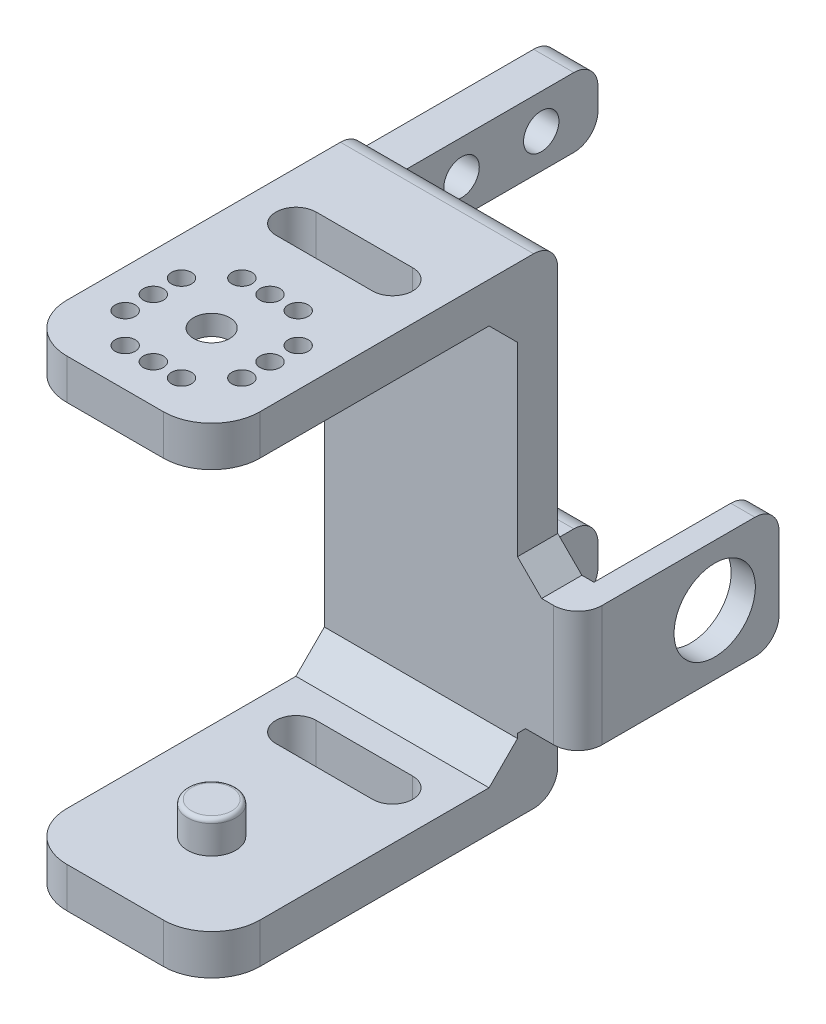
SolidWorks part; units mm, degrees
ref_plane "Front Plane" through (0, 0, 0) normal (0, 0, 1) x (1, 0, 0)
ref_plane "Top Plane" through (0, 0, 0) normal (0, 1, 0) x (1, 0, 0)
ref_plane "Right Plane" through (0, 0, 0) normal (1, 0, 0) x (0, 0, -1)
sketch "Sketch1" plane through (0, 0, 0) normal (1, 0, 0) x (0, 0, -1)
  line L0 (0, 59.7) -> (0, 0)
  line L1 (0, 0) -> (-43, 0)
  line L2 (-43, 0) -> (-43, 5)
  line L3 (-43, 5) -> (-8.5355, 5)
  line L4 (-5, 8.5355) -> (-5, 51.1645)
  line L5 (-8.5355, 54.7) -> (-43, 54.7)
  line L6 (-43, 54.7) -> (-43, 59.7)
  line L7 (-43, 59.7) -> (0, 59.7)
  line L8 (-8.5355, 54.7) -> (-5, 51.1645)
  line L9 (-5, 29.85) -> (0, 29.85) construction
  line L10 (-8.5355, 5) -> (-5, 8.5355)
  dimension "D1" = 49.7
  dimension "D2" = 5
  dimension "D3" = 5
  dimension "D4" = 5
  dimension "50" = 43
  dimension "D5" = 45
extrude "Boss-Extrude1" add sketch "Sketch1" along normal blind 24
sketch "Sketch2" plane through (0, 54.7, 0) normal (0, -1, 0) x (1, 0, 0)
  line L0 (24, 43) -> (0, 43) construction
  line L1 (12, 43) -> (12, 0) construction
  line L2 (24, 0) -> (0, 0) construction
  circle A0 centre (12, 31) radius 10.5
  dimension "D1" = 21
  dimension "D2" = 12
  dimension "D3" = 0
extrude "Cut-Extrude1" cut sketch "Sketch2" against normal blind 2.5
sketch "Sketch4" plane through (0, 57.2, 0) normal (0, -1, 0) x (1, 0, 0)
  circle A0 centre (12, 31) radius 2.25
  circle A1 centre (12, 31) radius 10.5 construction
  circle A2 centre (12, 38.25) radius 1.25
  circle A3 centre (8.5, 38.25) radius 1.25
  circle A4 centre (15.5, 38.25) radius 1.25
  circle A5 centre (19.25, 34.5) radius 1.25
  circle A6 centre (19.25, 31) radius 1.25
  circle A7 centre (19.25, 27.5) radius 1.25
  circle A8 centre (15.5, 23.75) radius 1.25
  circle A9 centre (12, 23.75) radius 1.25
  circle A10 centre (8.5, 23.75) radius 1.25
  circle A11 centre (4.75, 27.5) radius 1.25
  circle A12 centre (4.75, 31) radius 1.25
  circle A13 centre (4.75, 34.5) radius 1.25
  dimension "D1" = 4.5
  dimension "D2" = 0
  dimension "D3" = 2.5
  dimension "D4" = 7.25
  dimension "D5" = 3.5
  dimension "D6" = 3.5
  dimension "D7" = 4
extrude "Cut-Extrude2" cut sketch "Sketch4" against normal blind 10
sketch "Sketch11" plane through (0, 5, 0) normal (0, 1, 0) x (1, 0, 0)
  line L1 (24, -43) -> (0, -43) construction
  line L2 (12, -43) -> (12, -5) construction
  line L3 (24, -5) -> (0, -5) construction
  circle A0 centre (12, -31) radius 3
  dimension "D1" = 6
  dimension "D2" = 12
extrude "Boss-Extrude2" add sketch "Sketch11" along normal blind 4
sketch "Sketch12" plane through (0, 54.7, 0) normal (0, -1, 0) x (1, 0, 0)
  line L0 (12, 8.5355) -> (12, 20.5) construction
  line L2 (24, 8.5355) -> (0, 8.5355) construction
  line L3 (6, 12.0178) -> (18, 12.0178)
  line L10 (6, 17.0178) -> (18, 17.0178)
  line L11 (6, 12.0178) -> (18, 17.0178) construction
  line L12 (18, 12.0178) -> (6, 17.0178) construction
  line L17 (24, 43) -> (24, 0) construction
  circle A7 centre (12, 31) radius 10.5 construction
  arc A8 (18, 12.0178) -> (18, 17.0178) centre (18, 14.5178) ccw
  arc A9 (6, 12.0178) -> (6, 17.0178) centre (6, 14.5178) cw
  point P7 (12, 14.5178)
  point P18 (12, 14.5178)
  dimension "D1" = 5
  dimension "D2" = 6
extrude "Cut-Extrude5" cut sketch "Sketch12" against normal mid plane 130 contours A9 L10 A8 L3
sketch "Sketch13" plane through (0, 0, 0) normal (-1, 0, 0) x (0, 0, 1)
  line L0 (0, 8.6) -> (-24, 8.6)
  line L1 (0, 0) -> (0, 59.7) construction
  line L2 (-24, 8.6) -> (-24, 0)
  line L3 (-24, 0) -> (0, 0)
  line L4 (0, 0) -> (0, 8.6)
  line L5 (0, 28.85) -> (5, 28.85) construction
  line L11 (-12, 8.6) -> (-12, 0) construction
  line L12 (-24, 57.7) -> (0, 57.7)
  line L13 (-24, 49.1) -> (-24, 57.7)
  line L14 (0, 49.1) -> (-24, 49.1)
  line L15 (0, 57.7) -> (0, 49.1)
  line L16 (5, 51.1645) -> (5, 8.5355) construction
  circle A0 centre (-16.95, 4.3) radius 2.2
  circle A1 centre (-7.05, 4.3) radius 2.2
  circle A4 centre (-16.95, 53.4) radius 2.2
  circle A5 centre (-7.05, 53.4) radius 2.2
  dimension "D3" = 4.4
  dimension "D1" = 8.6
  dimension "D2" = 24
  dimension "D4" = 4.3
  dimension "D5" = 9.9
  dimension "D6" = 4.95
  dimension "D7" = 40.5
extrude "Boss-Extrude3" add sketch "Sketch13" against normal blind 5
sketch "Sketch14" plane through (24, 0, 0) normal (1, 0, 0) x (0, 0, -1)
  line L0 (-5, 10.1) -> (0, 10.1)
  line L1 (-5, 51.1645) -> (-5, 8.5355) construction
  line L2 (0, 0) -> (0, 59.7) construction
  line L3 (0, 10.1) -> (0, 25.1)
  line L4 (0, 25.1) -> (-5, 25.1)
  line L5 (-5, 25.1) -> (-5, 10.1)
  line L6 (-5, 17.6) -> (0, 17.6) construction
  line L7 (0, 8.6) -> (24, 8.6) construction
  dimension "D1" = 15
  dimension "D2" = 9
extrude "Boss-Extrude4" add sketch "Sketch14" along normal blind 7.5
sketch "Sketch15" plane through (0, 0, 0) normal (0, 0, -1) x (-1, 0, 0)
  line L0 (-31.5, 25.1) -> (-28.5, 25.1)
  line L1 (-31.5, 25.1) -> (-24, 25.1) construction
  line L2 (-28.5, 25.1) -> (-28.5, 10.1)
  line L3 (-31.5, 10.1) -> (-24, 10.1) construction
  line L4 (-28.5, 10.1) -> (-31.5, 10.1)
  line L5 (-31.5, 10.1) -> (-31.5, 25.1)
  dimension "D1" = 3
extrude "Boss-Extrude5" add sketch "Sketch15" along normal blind 20
sketch "Sketch16" plane through (28.5, 0, 0) normal (-1, 0, 0) x (0, 0, 1)
  line L0 (0, 8.6) -> (0, 49.1) construction
  line L1 (-20, 10.1) -> (-20, 25.1) construction
  circle A0 centre (-12, 17.6) radius 5.05
  point P7 (-20, 17.6)
  dimension "D1" = 10.1
  dimension "D2" = 12
extrude "Cut-Extrude6" cut sketch "Sketch16" against normal through all
chamfer "Chamfer1" distance 3 angle 45 1 edges at (24, 25.1, 2.5)
chamfer "Chamfer2" distance 1 angle 45 1 edges at (24, 10.1, 2.5)
fillet "Fillet2" radius 6 4 edges at (24, 2.5, 43) (0, 2.5, 43) (24, 57.2, 43) (0, 57.2, 43)
fillet "Fillet7" radius 3 9 edges at (12, 59.7, 0) (2.5, 0, -24) (2.5, 8.6, -24) (2.5, 49.1, -24) (2.5, 57.7, -24) (31.5, 17.6, 5) (30, 10.1, -20) (30, 25.1, -20) (14.5, 0, 0)
fillet "Fillet8" radius 0.5 1 edges at (12, 9, 34)
